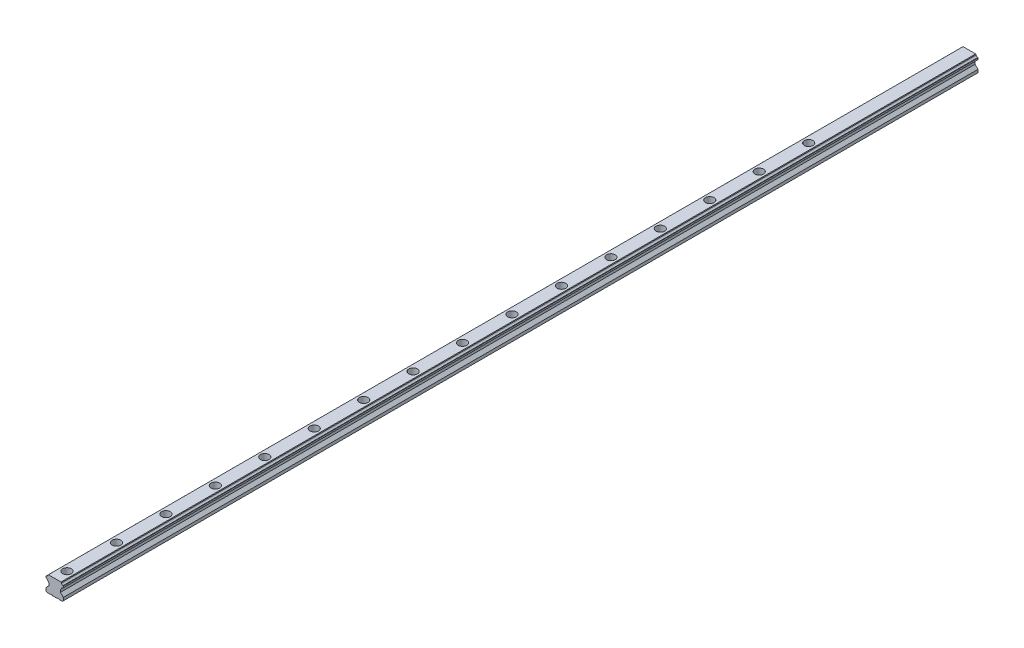
SolidWorks part; units mm, degrees
material "Plain Carbon Steel"
ref_plane "Front Plane" through (0, 0, 0) normal (0, 0, 1) x (1, 0, 0)
ref_plane "Top Plane" through (0, 0, 0) normal (0, 1, 0) x (1, 0, 0)
ref_plane "Right Plane" through (0, 0, 0) normal (1, 0, 0) x (0, 0, -1)
sketch "Sketch1" plane through (-20, 0, 0) normal (0, 0, 1) x (1, 0, 0)
  line L0 (6, 22.215) -> (6, 19.7791)
  line L1 (6, 19.7791) -> (6.4691, 19.31)
  line L2 (9.0004, 16.7787) -> (10.6997, 15.0794)
  line L3 (10.6997, 15.0794) -> (10.6997, 10.9996)
  line L4 (10.6997, 10.9996) -> (6, 6.3)
  line L5 (6, 6.3) -> (6, 1.5)
  line L6 (6, 1.5) -> (7.5, 0)
  line L7 (7.5, 0) -> (12.25, 0)
  line L8 (12.25, 0) -> (12.75, 0.5)
  line L9 (12.75, 0.5) -> (16.25, 0.5)
  line L10 (16.25, 0.5) -> (16.75, 0)
  line L11 (16.75, 0) -> (23.25, 0)
  line L12 (20, 26) -> (20, 0) construction
  line L13 (33.5309, 22.6905) -> (34, 22.215)
  line L14 (30.2142, 26) -> (30.9996, 25.2147)
  line L15 (23.75, 0.5) -> (23.25, 0)
  line L16 (27.25, 0.5) -> (23.75, 0.5)
  line L17 (27.75, 0) -> (27.25, 0.5)
  line L18 (32.5, 0) -> (27.75, 0)
  line L19 (34, 1.5) -> (32.5, 0)
  line L20 (34, 6.3) -> (34, 1.5)
  line L21 (29.3003, 10.9996) -> (34, 6.3)
  line L22 (29.3003, 15.0794) -> (29.3003, 10.9996)
  line L23 (30.9996, 16.7787) -> (29.3003, 15.0794)
  line L24 (34, 19.7791) -> (33.5309, 19.31)
  line L25 (30.2142, 26) -> (9.7858, 26)
  line L26 (9.7858, 26) -> (9.0004, 25.2147)
  line L27 (6.4691, 22.6905) -> (6, 22.215)
  line L28 (34, 22.215) -> (34, 19.7791)
  arc A0 (6.4691, 19.31) -> (9.0004, 16.7787) centre (6.1304, 16.4399) cw
  arc A1 (30.9996, 25.2147) -> (33.5309, 22.6905) centre (33.8688, 25.5607) ccw
  arc A2 (33.5309, 19.31) -> (30.9996, 16.7787) centre (33.8696, 16.4399) ccw
  arc A3 (9.0004, 25.2147) -> (6.4691, 22.6905) centre (6.1312, 25.5607) cw
  dimension "D19" = 2.89
  dimension "D24" = 3.3095
  dimension "D1" = 26
  dimension "D2" = 28
  dimension "D3" = 6.5
  dimension "D4" = 0.5
  dimension "D5" = 3.5
  dimension "D6" = 0.5
  dimension "D7" = 0.5
  dimension "D8" = 1.5
  dimension "D9" = 1.5
  dimension "D10" = 4.8
  dimension "D11" = 4.6996
  dimension "D12" = 4.6997
  dimension "D13" = 4.0798
  dimension "D14" = 1.6993
  dimension "D15" = 1.6993
  dimension "D16" = 20.4285
  dimension "D17" = 0.7853
  dimension "D18" = 0.4691
  dimension "D20" = 0.7853
  dimension "D21" = 0.4755
  dimension "D22" = 2.4359
  dimension "D23" = 0.4691
extrude "Extrude1" add sketch "Sketch1" against normal blind 1480
sketch "Sketch2" plane through (0, 0, 0) normal (1, 0, 0) x (0, 0, -1)
  line L0 (20, 26) -> (27, 26)
  line L1 (27, 26) -> (27, 14)
  line L2 (27, 14) -> (24.5, 14)
  line L3 (24.5, 14) -> (24.5, 0)
  line L4 (24.5, 0) -> (20, 0)
  line L5 (20, 0) -> (20, 26) construction
  line L6 (20, 0) -> (20, 26) construction
  line L7 (20, 26) -> (20, 0)
  line L8 (1480, 0) -> (0, 0) construction
  line L9 (1480, 26) -> (0, 26) construction
  dimension "D1" = 14
  dimension "D2" = 9
  dimension "D3" = 12
  dimension "D4" = 20
revolve "Cut-Revolve1" cut sketch "Sketch2" angle 360 about L6 reverse direction yes
ref_axis "Axis1" through (0, 0, -294) along (0, 0, 1)
pattern_linear "LPattern1" count 16 spacing 80 along (0, 0, -1) of "Cut-Revolve1"
